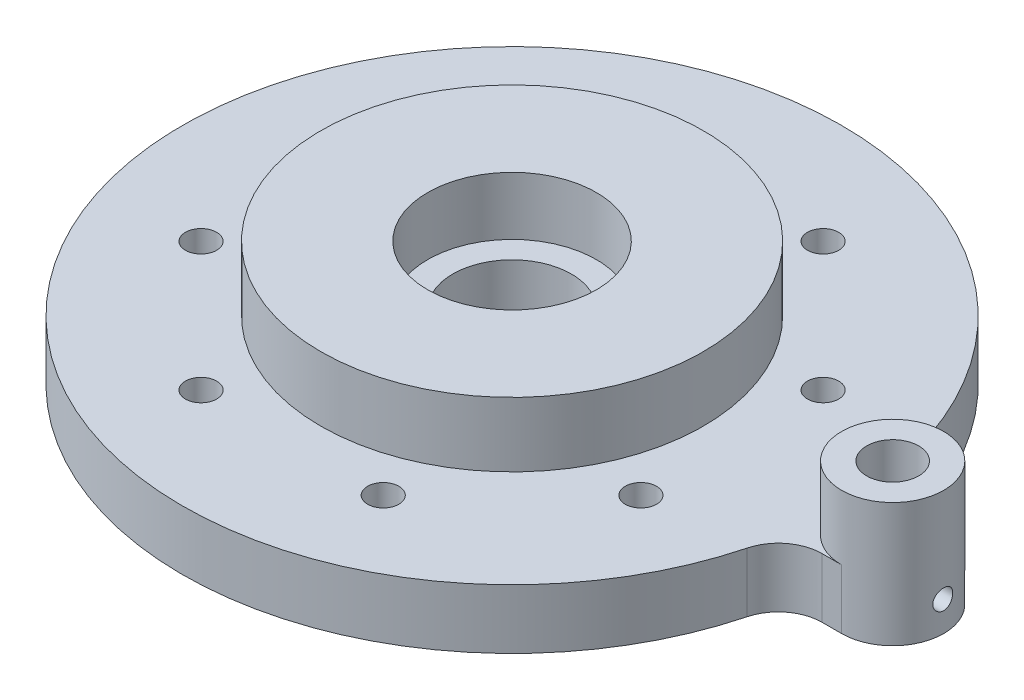
SolidWorks part; units mm, degrees
material "1060 Alloy"
ref_plane "Front" through (0, 0, 0) normal (0, 0, 1) x (1, 0, 0)
ref_plane "Top" through (0, 0, 0) normal (0, 1, 0) x (1, 0, 0)
ref_plane "Right" through (0, 0, 0) normal (1, 0, 0) x (0, 0, -1)
sketch "Sketch1" plane through (0, 0, 0) normal (0, 1, 0) x (1, 0, 0)
  line L0 (52.75, 0) -> (60.9172, 0) construction
  line L1 (57.7929, 8.1672) -> (60.9172, 8.1672)
  line L2 (57.7929, -8.1672) -> (60.9172, -8.1672)
  line L3 (52.75, 0) -> (69.0844, 0) construction
  arc A0 (51.0222, 13.3903) -> (51.0222, -13.3903) centre (0, 0) ccw
  circle A1 centre (0, 0) radius 52.75 construction
  arc A2 (60.9172, -8.1672) -> (60.9172, 8.1672) centre (60.9172, 0) ccw
  arc A3 (51.0222, 13.3903) -> (57.7929, 8.1672) centre (57.7929, 15.1672) ccw
  arc A4 (57.7929, -8.1672) -> (51.0222, -13.3903) centre (57.7929, -15.1672) ccw
  point P5 (34.5422, 0)
  point P10 (52.1139, 8.1672)
  dimension "D1" = 105.5
  dimension "D4" = 7
  dimension "D2" = 16.3344
  dimension "D3" = 16.3344
extrude "base" add sketch "Sketch1" along normal blind 9.525
sketch "Sketch2" plane through (0, 9.525, 0) normal (0, 1, 0) x (1, 0, 0)
  line L0 (60.9172, 8.1672) -> (60.9172, -8.1672) construction
  circle A0 centre (0, 0) radius 30.6267
  arc A1 (60.9172, -8.1672) -> (60.9172, 8.1672) centre (60.9172, 0) ccw construction
  circle A2 centre (60.9172, 0) radius 8.1672
  circle A3 centre (60.9172, 0) radius 4.1672
  dimension "D1" = 61.2534
  dimension "D2" = 8.3344
sketch "Sketch3" plane through (0, 0, 0) normal (0, -1, 0) x (1, 0, 0)
  line L0 (0, 0) -> (69.0844, 0) construction
  line L1 (0, 0) -> (37.2999, -37.2999) construction
  circle A0 centre (0, 0) radius 40.75 construction
  circle A1 centre (-28.8146, -28.8146) radius 3.5
  circle A2 centre (-28.8146, 28.8146) radius 3.5
  circle A3 centre (28.8146, 28.8146) radius 3.5
  circle A4 centre (28.8146, -28.8146) radius 3.5
  arc A5 (60.9172, -8.1672) -> (60.9172, 8.1672) centre (60.9172, 0) ccw construction
  arc A6 (51.0222, 13.3903) -> (51.0222, -13.3903) centre (0, 0) ccw construction
  point P2 (0, 0)
  point P14 (0, 0)
  dimension "D1" = 81.5
  dimension "D2" = 7
  dimension "D4" = 45
  dimension "D3" = 4
extrude "square bolt holes" cut sketch "Sketch3" against normal blind 7.525
sketch "Sketch4" plane through (0, 9.525, 0) normal (0, 1, 0) x (1, 0, 0)
  line L0 (0, 0) -> (0, 38.1) construction
  line L1 (0, 38.1) -> (0, 0) construction
  line L2 (0, 0) -> (14.5802, 35.1998) construction
  circle A0 centre (0, 0) radius 38.1 construction
  circle A1 centre (14.5802, 35.1998) radius 2.5
  dimension "D1" = 76.2
  dimension "D3" = 5
  dimension "D2" = 22.5
extrude "housing bolts" cut sketch "Sketch4" against normal blind 44.33
pattern_circular "CirPattern1" count 8 over 360 about axis through (0, 9.525, 0) along (0, 1, 0) of "housing bolts"
extrude "impeller cavity riser" add sketch "Sketch2" along normal blind 10.3296
sketch "Sketch5" plane through (0, 19.8545, 0) normal (0, 1, 0) x (1, 0, 0)
  circle A0 centre (0, 0) radius 13.5
  dimension "D1" = 27
extrude "seal bore" cut sketch "Sketch5" against normal blind 9.3
sketch "Sketch6" plane through (0, 10.5545, 0) normal (0, 1, 0) x (1, 0, 0)
  circle A0 centre (0, 0) radius 9.5
  dimension "D1" = 19
extrude "bore" cut sketch "Sketch6" against normal blind 39.3
sketch "pressure tap plane alignment" plane through (0, 0, 0) normal (0, -1, 0) x (1, 0, 0)
  line L1 (0, 0) -> (52.75, 0) construction
  line L2 (52.75, 0) -> (52.75, 52.75) construction
  line L3 (52.75, 52.75) -> (0, 52.75) construction
  circle A0 centre (0, 0) radius 52.75 construction
  circle A1 centre (0, 0) radius 52.75 construction
  point P1 (52.75, 0)
  point P10 (52.75, 0)
ref_plane "pressure tap plane" through (52.75, 0, 0) normal (1, 0, 0) x (0, 0, -1)
sketch "Sketch9" plane through (52.75, 0, 0) normal (1, 0, 0) x (0, 0, -1)
  line L0 (0, 0) -> (0, 9.525) construction
  line L1 (52.75, 9.525) -> (-52.75, 9.525) construction
  circle A0 centre (0, 4.7625) radius 1.5875
  dimension "D1" = 3.175
extrude "pressure tap" cut sketch "Sketch9" against normal blind 52.75 and the other way through all
sketch "Sketch10" plane through (0, 9.525, 0) normal (0, 1, 0) x (1, 0, 0)
  circle A0 centre (60.9172, 0) radius 1.5875
  dimension "D1" = 3.175
extrude "pressure tap vertical hole" cut sketch "Sketch10" against normal blind 6.35
equation "\"bearing OD\" = 30mm"
equation "\"bearing ID\"= 10mm"
equation "\"bearing depth\"= 9mm"
equation "\"bearing outer race thickness\"= 1mm"
equation "\"bearing inner race thickness\"= 1mm"
equation "\"bearing bore\" = \"bearing depth\" + 1mm"
equation "\"small seal OD\" = 20mm"
equation "\"small seal ID\"= 8mm"
equation "\"small seal depth\" = 8.3mm"
equation "\"small seal bore\" = \"small seal depth\" + 1mm"
equation "\"big seal OD\" = 27mm"
equation "\"big seal ID\"= 15mm"
equation "\"big seal depth\"= 8.3mm"
equation "\"big seal bore\" = \"big seal depth\" + 1mm"
equation "\"z\" = 8 \t\t'number of blades"
equation "\"de\" = 0.426in \t\t'entrance eye diameter"
equation "\"d2\" = 2.097in \t\t'outer diameter of the impeller "
equation "\"d_exit\" = 0.18in \t'volute throat aka D4"
equation "\"theta\" = 15"
equation "\"b2\" = .071in\t\t\t\t\t\t\t'tip height from disc surface at d2"
equation "\"b1\" = \"b2\" + (\"d2\"/2 - \"de\"/2)*sin(\"theta\")\t\t\t'tip height from disc surface at inlet eye"
equation "\"s\" = ( 1/\"z\")*(3.14*\"de\" - (3.14*(\"de\"^2) / (4*(\"b1\"))))\t'thickness of blades, calculated from area"
equation "\"s_opening\" = (3.14*\"de\" - \"z\"*\"s\")/\"z\"\t\t\t\t'ideal gap between blades, calculated from area"
equation "\"area_eye\"=3.14*(\"de\"^2)/4\t\t\t\t\t'eye area"
equation "\"single_channel_area\"=\"s_opening\"*\"b1\"\t\t\t\t'ideal area between two blades"
equation "\"minimum channel width\" = \"s_opening\"\t\t\t\t\t\t\t'minimum s, set this to a bit size for milling or to s_opening for DMLS"
equation "\"inlet area before cut\" = \"minimum channel width\" * (\"z\") * \"b1\"\t\t\t'if minimum channel width>s_opening, this is larger than area_eye"
equation "\"area to cut\" = \"inlet area before cut\" - \"area_eye\"\t\t\t\t\t'amount of extra area\t\t\t\t\t"
equation "\"height to cut\" = \"area to cut\" / ((\"z\")* \"minimum channel width\")+ .0001in\t\t'the 0.0001 in cut is to avoid errors in model"
equation "\"final impeller center height\" = \"impeller base thickness\" + \"b1\" - \"height to cut\"\t'corrected height so that sum of channel areas equals eye area"
equation "\"impeller upper clearance\"= .5mm"
equation "\"impeller horizontal clearance\"= (\"d2\"*1.15 - \"d2\")/2 \t\t\t\t\t'clearance based on D2-D3 ratio for circular volute, ranges 1.15 to 1.2"
equation "\"impeller bottom clearance\"= .5mm"
equation "\"impeller base thickness\"= 2mm"
equation "\"impeller dowel diameter\" = 2mm"
equation "\"impeller bolt head diameter\" = 7.5mm"
equation "\"impeller bolt head depth\" = 4mm"
equation "\"impeller bolt stop depth\" = 3mm"
equation "\"impeller bolt bore\" = 4mm"
equation "\"impeller shaft bore depth\" = 12mm"
equation "\"impeller shaft bore\" = 8mm"
equation "\"impeller boss depth\" = \"impeller shaft bore depth\"+\"impeller bolt stop depth\"+\"impeller bolt head depth\"-\"impeller base thickness\""
equation "\"impeller boss diameter\" = \"big seal ID\""
equation "\"impeller dowel length\" = 2mm*2 + \"impeller shaft bore\""
equation "\"coupler motor shaft hole ID\"= 8mm"
equation "\"coupler OD\"= 17mm"
equation "\"coupler length\"= 25mm"
equation "\"motor OD\" = 64mm"
equation "\"motor shaft diameter\"= 8mm"
equation "\"motor shaft pride\"= 32mm"
equation "\"motor to bearing plate distance\" = \"motor shaft pride\" + 2mm +\"coupler length\"/2"
equation "\"square plate bolt bore\" = 8mm"
equation "\"square plate bolt head diameter\" = 13.5mm"
equation "\"square plate bolt pattern diameter\"= \"motor OD\" + \"square plate bolt head diameter\" + 4mm"
equation "\"motor mount center bore\"= \"coupler OD\"+ 4mm"
equation "\"motor mount post radius\"= ( 3 * \"square plate bolt bore\" ) / 2"
equation "\"motor mount m4 screw hole diameter\"= 4mm"
equation "\"motor mount m4 head diameter\"= 7.25mm"
equation "\"motor mount m4 head depth\"= 4mm"
equation "\"motor mount m4 pattern diamater\" = 30mm"
equation "\"motor mount plate thickness\"= 8mm + \"motor mount m4 head depth\""
equation "\"bearing plate stop ID\" = \"bearing OD\" - 4mm"
equation "\"bearing plate stop depth\" = 3mm"
equation "\"bearing plate thickness\" = \"bearing bore\" + \"bearing plate stop depth\" + \"shaft bearing stop length\""
equation "\"small seal plate lip depth\" = 2mm"
equation "\"small seal plate lip ID\" = \"small seal OD\" - 3mm"
equation "\"small seal plate thickness\" = \"small seal plate lip depth\" + \"small seal bore\""
equation "\"shaft coupler section diameter\" = 8mm"
equation "\"shaft coupler section length\" = \"motor to bearing plate distance\" - \"motor shaft pride\" - 2mm"
equation "\"shaft bearing section diameter\" = \"bearing ID\""
equation "\"shaft bearing section length\" = \"bearing plate stop depth\" + \"bearing depth\""
equation "\"shaft bearing stop diameter\" = \"bearing ID\" + 4mm"
equation "\"shaft bearing stop length\" = 3mm"
equation "\"shaft small seal section diameter\" = \"small seal ID\""
equation "\"shaft small seal section length\" = \"small seal plate thickness\" + 1mm"
equation "\"big seal plate thickness\" = \"big seal plate pressure hole diameter\"*3"
equation "\"big seal plate riser\" = \"impeller housing thickness\"/2 - \"b2\"/2 - \"impeller base thickness\" - \t\"impeller bottom clearance\"\t\t\t'this offsets the gap under the housing"
equation "\"big seal plate pressure hole diameter\" = .125in\t'this is 1/8 drill "
equation "\"big seal plate pressure tap diameter\" = .328125in \t'this is 21/64 drill for a 1/8 ANPT tap"
equation "\"big seal plate pressure tap grip\" = 4mm\t\t'this is the area around the tap so it doesn't crack"
equation "\"big seal plate pressure tap depth\" = 12"
equation "\"impeller cavity center height\"= \"impeller bottom clearance\" + \"impeller upper clearance\" + \"final impeller center height\""
equation "\"impeller cavity diameter\"= 2 * \"impeller horizontal clearance\" + \"d2\" \t\t\t\t\t\t\t\t\t'called D3 analytically"
equation "\"impeller cavity outer height\"= \"impeller bottom clearance\" + \"impeller upper clearance\" + \"impeller base thickness\" + \"b2\" \t\t'this is height at impeller diameter d2, not at d3"
equation "\"impeller housing thickness\"= \"impeller housing exit threaded diameter\" + 2*\"impeller housing outlet grip\""
equation "\"impeller housing diameter\" = \"square plate bolt pattern diameter\" + 2*\"motor mount post radius\""
equation "\"impeller housing bolt count\" = 8"
equation "\"impeller housing bolt diameter\" = 6mm"
equation "\"impeller housing bolt pattern diameter\" = 3in"
equation "\"impeller housing threaded inlet diameter\" = 0.6875in \t\t'this is the 11/16 drill size for 1/2 npt fitting"
equation "\"impeller housing threaded inlet depth\"= 15mm"
equation "\"impeller housing exit threaded diameter\"= 0.6875in \t\t'this is the 11/16 drill size for 1/2 npt fitting"
equation "\"impeller housing exit threaded depth\"= 18mm"
equation "\"impeller housing diffuser conical angle\"=10"
equation "\"impeller housing diffuser tangent angle\"=5"
equation "\"impeller housing outlet grip\" = 5mm"
equation "\"D1@Sketch1\"=\"impeller housing diameter\""
equation "\"big seal plate lip ID\" = \"big seal OD\" - 3mm"
equation "\"D1@base\" = \"big seal plate thickness\""
equation "\"D1@Sketch2\"=\"impeller cavity diameter\""
equation "\"D1@Sketch3\"=\"square plate bolt pattern diameter\""
equation "\"D2@Sketch3\"=\"square plate bolt bore\"-1mm"
equation "\"D1@square bolt holes\"=\"big seal plate thickness\" - 2mm"
equation "\"D1@Sketch4\"=\"impeller housing bolt pattern diameter\""
equation "\"D2@Sketch4\"=360/\"impeller housing bolt count\"/2"
equation "\"D3@Sketch4\"=\"impeller housing bolt diameter\"-1mm"
equation "\"D1@CirPattern1\"=\"impeller housing bolt count\""
equation "\"D1@impeller cavity riser\" = \"big seal plate riser\""
equation "\"D1@Sketch5\"=\"big seal OD\""
equation "\"D1@seal bore\" = \"big seal bore\""
equation "\"D1@Sketch6\"=\"big seal ID\"+4mm"
equation "\"D1@Sketch9\"=\"big seal plate pressure hole diameter\""
equation "\"D1@pressure tap\"=\"impeller housing diameter\"/2"
equation "\"de_length\" = 10mm\t'entrance eye consistent length"
equation "\"square plate bolt head depth\" = 8mm"
equation "\"shaft impeller section diameter\" = \"impeller shaft bore\""
equation "\"shaft impeller section length\" = \"big seal plate thickness\" + \"big seal plate riser\" + \"impeller bottom clearance\" + \"impeller base thickness\" - \"impeller bolt head depth\" - \"impeller bolt stop depth\""
equation "\"impeller housing diffuser final diameter\" = .5in"
equation "\"D2@Sketch1\"=\"big seal plate pressure tap diameter\" + \"big seal plate pressure tap grip\"*2"
equation "\"D3@Sketch1\"=\"big seal plate pressure tap diameter\" + \"big seal plate pressure tap grip\"*2"
equation "\"D2@pressure tap\"=\"big seal plate pressure tap diameter\"/2+\"big seal plate pressure tap grip\""
equation "\"D2@Sketch2\"=\"big seal plate pressure tap diameter\""
equation "\"D1@Sketch10\"=\"big seal plate pressure hole diameter\""
equation "\"D1@pressure tap vertical hole\" = \"big seal plate thickness\" / 2 + \"big seal plate pressure hole diameter\" / 2"
